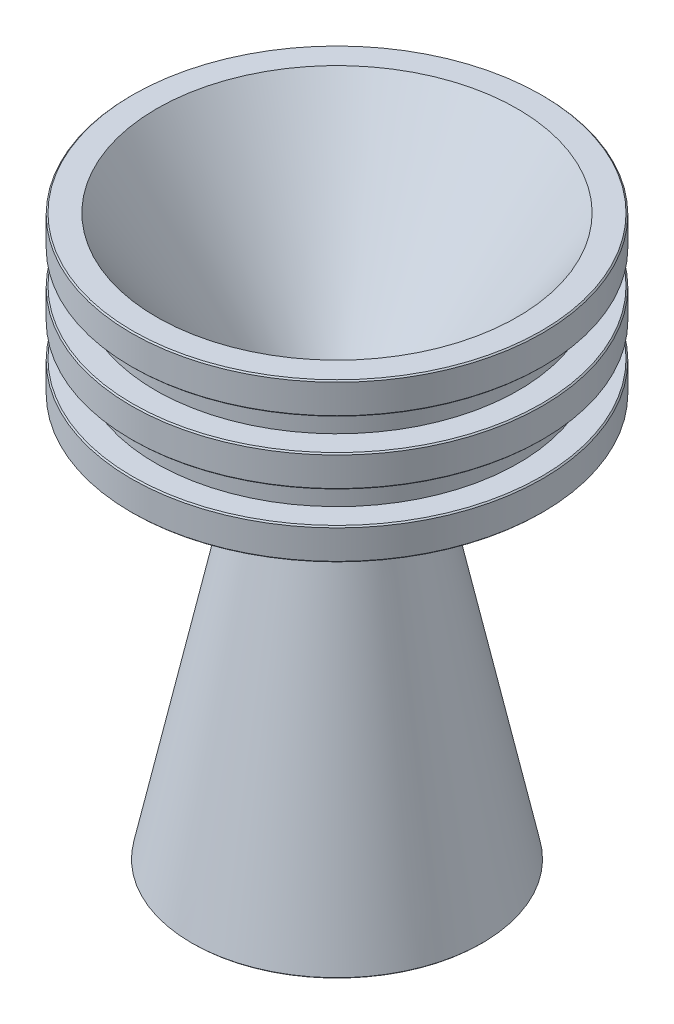
SolidWorks part; units mm, degrees
ref_plane "Front Plane" through (0, 0, 0) normal (0, 0, 1) x (1, 0, 0)
ref_plane "Top Plane" through (0, 0, 0) normal (0, 1, 0) x (1, 0, 0)
ref_plane "Right Plane" through (0, 0, 0) normal (1, 0, 0) x (0, 0, -1)
sketch "Sketch1" plane through (0, 0, 0) normal (0, 0, 1) x (1, 0, 0)
  line L0 (0, 0) -> (2.54, 0)
  line L8 (0, 0) -> (0, -3.175)
  line L9 (0, -3.175) -> (2.4447, -3.175)
  line L10 (2.4447, -3.175) -> (2.4448, -6.35)
  line L11 (2.4448, -6.35) -> (0, -6.35)
  line L12 (0, -6.35) -> (0, -9.525)
  line L13 (0, -9.525) -> (2.4447, -9.525)
  line L14 (2.4447, -9.525) -> (2.4448, -12.7)
  line L15 (2.4448, -12.7) -> (0, -12.7)
  line L16 (0, -12.7) -> (0, -15.875)
  line L18 (0, 0) -> (20.701, 0) construction
  line L19 (20.701, 0) -> (20.701, -56.4388) construction
  line L20 (2.54, 0) -> (16.51, -19.9512)
  line L22 (9.2942, -56.4388) -> (6.0483, -56.4388)
  line L24 (16.51, -19.9512) -> (16.51, -22.4912)
  line L25 (16.51, -22.4912) -> (9.2942, -56.4388)
  line L27 (20.701, -56.4388) -> (9.2942, -56.4388) construction
  line L29 (9.7798, -15.875) -> (0, -15.875)
  line L30 (13.2641, -22.4912) -> (16.51, -22.4912) construction
  line L33 (13.2641, -20.851) -> (9.7798, -15.875)
  line L34 (13.2641, -22.4912) -> (6.0483, -56.4388)
  line L35 (13.2641, -20.851) -> (13.2641, -22.4912)
  line L36 (13.2641, -20.851) -> (16.51, -19.9512) construction
  dimension "D1" = 2.54
  dimension "D2" = 18.2562
  dimension "D3" = 3.175
  dimension "D4" = 3.175
  dimension "D5" = 3.175
  dimension "D6" = 20.701
  dimension "D7" = 2.54
  dimension "D8" = 35
  dimension "D9" = 12
  dimension "D10" = 3.175
  dimension "D11" = 4.191
  dimension "D12" = 3.175
  dimension "D13" = 3.175
  dimension "D14" = 56.4388
  dimension "D15" = 14.6527
  dimension "D16" = 33.9476
  dimension "D17" = 56.4388
  dimension "D18" = 15.875
  dimension "D19" = 11.4068
revolve "base_revolve" add sketch "Sketch1" angle 360 about L19
chamfer "outer_chamfers" distance 0.127 angle 45 7 edges at (0, -15.875, 0) (0, 0, 0) (6.0483, -56.4388, 0) (0, -9.525, 0) (0, -12.7, 0) (0, -6.35, 0) (0, -3.175, 0) first distance on face at (9.7798, -15.875, 0) first distance on face at (0, -3.175, 0) first distance on face at (9.2942, -56.4388, 0) first distance on face at (2.4447, -9.525, 0) first distance on face at (0, -12.7, 0) first distance on face at (0, -9.525, 0) first distance on face at (2.4447, -3.175, 0)
